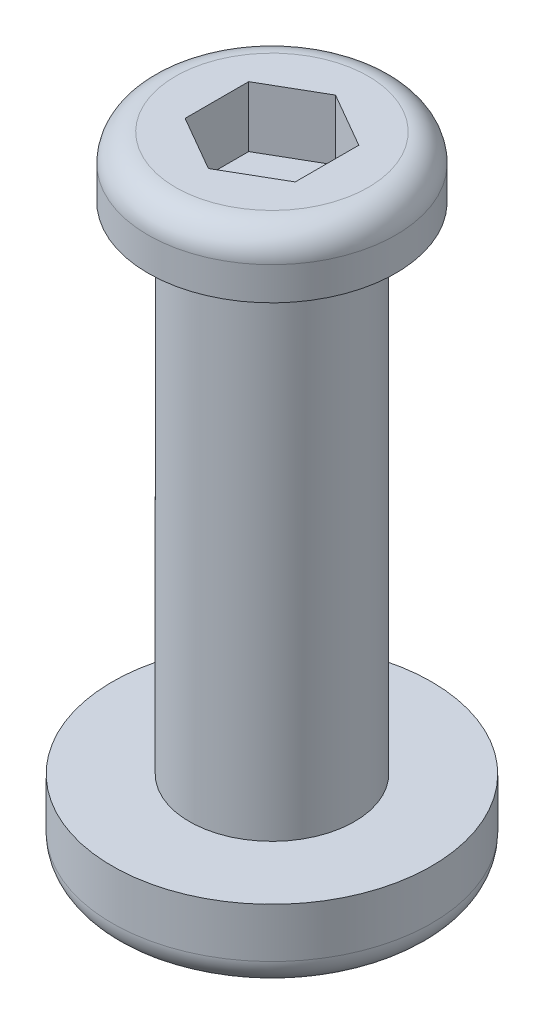
SolidWorks part; units mm, degrees
material "AISI 304"
ref_plane "前视基准面" through (0, 0, 0) normal (0, 0, 1) x (1, 0, 0)
ref_plane "上视基准面" through (0, 0, 0) normal (0, 1, 0) x (1, 0, 0)
ref_plane "右视基准面" through (0, 0, 0) normal (1, 0, 0) x (0, 0, -1)
other "Configuration Table"
sketch "草图1" plane through (0, 0, 0) normal (0, 1, 0) x (1, 0, 0)
  circle A0 centre (0, 0) radius 1.5
  dimension "D1" = 3
extrude "凸台-拉伸1" add sketch "草图1" along normal blind 9
sketch "草图2" plane through (0, 9, 0) normal (0, 1, 0) x (1, 0, 0)
  line L0 (0, 0) -> (0, 1.8449) construction
  line L1 (0, 1.1547) -> (-1, 0.5774)
  line L2 (-1, 0.5774) -> (-1, -0.5774)
  line L3 (-1, -0.5774) -> (0, -1.1547)
  line L4 (0, -1.1547) -> (1, -0.5774)
  line L5 (1, -0.5774) -> (1, 0.5774)
  line L6 (1, 0.5774) -> (0, 1.1547)
  circle A0 centre (0, 0) radius 2.25
  circle A1 centre (0, 0) radius 1 construction
  dimension "D2" = 4.5
  dimension "D1" = 2
extrude "凸台-拉伸2" add sketch "草图2" along normal blind 1.1
sketch "草图3" plane through (0, 0, 0) normal (0, -1, 0) x (1, 0, 0)
  line L0 (0, 0) -> (0, 3.3681) construction
  line L1 (0, 1.1547) -> (-1, 0.5774)
  line L2 (-1, 0.5774) -> (-1, -0.5774)
  line L3 (-1, -0.5774) -> (0, -1.1547)
  line L4 (0, -1.1547) -> (1, -0.5774)
  line L5 (1, -0.5774) -> (1, 0.5774)
  line L6 (1, 0.5774) -> (0, 1.1547)
  circle A0 centre (0, 0) radius 2.9
  circle A1 centre (0, 0) radius 1 construction
  dimension "D2" = 5.8
  dimension "D1" = 2
extrude "凸台-拉伸3" add sketch "草图3" along normal blind 1.4
fillet "圆角1" radius 0.5 2 edges at (0, 10.1, 2.25) (0, -1.4, -2.9)
